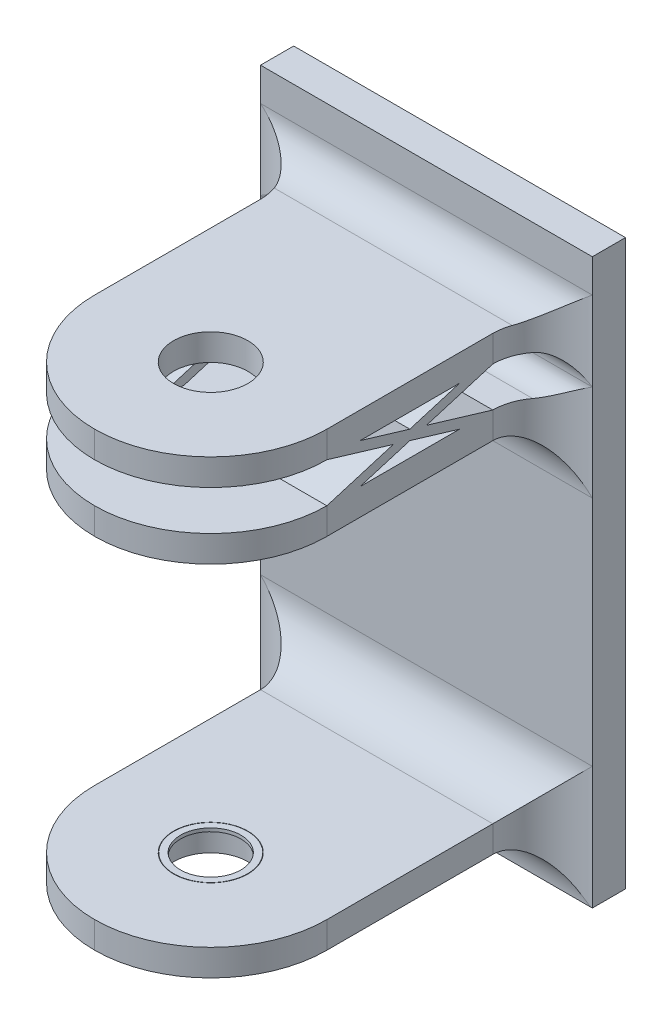
SolidWorks part; units mm, degrees
ref_plane "Plan de face" through (0, 0, 0) normal (1, 0, 0) x (0, 1, 0)
ref_plane "Plan de dessus" through (0, 0, 0) normal (0, 0, 1) x (0, 1, 0)
ref_plane "Plan de droite" through (0, 0, 0) normal (0, 1, 0) x (-1, 0, 0)
sketch "Esquisse1" plane through (0, 0, 0) normal (0, 0, 1) x (0, 1, 0)
  line L1 (0, 0) -> (150, 0)
  line L2 (0, 0) -> (0, 100)
  line L3 (0, 100) -> (150, 100)
  line L4 (150, 0) -> (150, 100)
  dimension "D1" = 150
  dimension "D2" = 100
extrude "Boss.-Extru.1" add sketch "Esquisse1" along normal blind 10
sketch "Esquisse2" plane through (0, 0, 10) normal (0, 0, 1) x (1, 0, 0)
  line L0 (-100, 150) -> (-100, 0) construction
  line L1 (-85, 130) -> (-15, 130)
  line L2 (-85, 130) -> (-85, 122)
  line L3 (-85, 122) -> (-15, 122)
  line L4 (-15, 130) -> (-15, 122)
  line L5 (-85, 150) -> (-15, 150)
  line L6 (0, 0) -> (0, 150) construction
  line L7 (0, 150) -> (-100, 150) construction
  line L8 (-85, 22) -> (-15, 22)
  line L9 (-85, 22) -> (-85, 14)
  line L10 (-85, 14) -> (-15, 14)
  line L11 (-15, 22) -> (-15, 14)
  line L12 (-85, 150) -> (-85, 142)
  line L13 (-85, 142) -> (-15, 142)
  line L14 (-15, 150) -> (-15, 142)
  dimension "D1" = 8
  dimension "D2" = 8
  dimension "D3" = 100
  dimension "D4" = 70
  dimension "D5" = 15
  dimension "D6" = 70
  dimension "D7" = 15
  dimension "D8" = 12
  dimension "D9" = 70
  dimension "D10" = 8
  dimension "D11" = 15
extrude "Boss.-Extru.2" add sketch "Esquisse2" along normal blind 100
fillet "Congé1" radius 35 6 edges at (-85, 126, 110) (-15, 126, 110) (-15, 18, 110) (-85, 18, 110) (-85, 146, 110) (-15, 146, 110)
sketch "Esquisse3" plane through (0, 150, 0) normal (0, 1, 0) x (-1, 0, 0)
  line L0 (0, 10) -> (0, 0) construction
  line L2 (0, 0) -> (100, 0) construction
  circle A0 centre (50, 75) radius 11.2
  dimension "D3" = 22.4
  dimension "D1" = 50
  dimension "D2" = 75
extrude "Enlèv. mat.-Extru.1" cut sketch "Esquisse3" against normal blind 150
fillet "Congé2" radius 15 9 edges at (-15, 18, 10) (-50, 22, 10) (-85, 18, 10) (-50, 14, 10) (-85, 146, 10) (-15, 146, 10) (-15, 126, 10) (-50, 122, 10) (-85, 126, 10)
fillet "Congé3" radius 6 2 edges at (-50, 142, 10) (-50, 130, 10)
sketch "Esquisse4" plane through (0, 0, 0) normal (0, -1, 0) x (1, 0, 0)
  line L0 (-100, 10) -> (0, 10) construction
  line L1 (-85.0784, 7.5) -> (-65.0784, 7.5)
  line L2 (-85.0784, 7.5) -> (-85.0784, 2.5)
  line L3 (-85.0784, 2.5) -> (-65.0784, 2.5)
  line L4 (-65.0784, 7.5) -> (-65.0784, 2.5)
  line L5 (-30.993, 7.5) -> (-10.993, 7.5)
  line L6 (-30.993, 7.5) -> (-30.993, 2.5)
  line L7 (-30.993, 2.5) -> (-10.993, 2.5)
  line L8 (-10.993, 7.5) -> (-10.993, 2.5)
  dimension "D1" = 20
  dimension "D2" = 5
  dimension "D3" = 2.5
  dimension "D4" = 5
  dimension "D5" = 20
  dimension "D6" = 2.5
extrude "Enlèv. mat.-Extru.2" cut sketch "Esquisse4" against normal blind 10
sketch "Esquisse5" plane through (-85, 0, 0) normal (-1, 0, 0) x (0, -1, 0)
  line L0 (-142, 75) -> (-130, 35)
  line L1 (-130, 75) -> (-130, 25) construction
  line L2 (-130, 35) -> (-130, 25)
  line L3 (-130, 25) -> (-142, 65)
  line L4 (-142, 75) -> (-142, 25) construction
  line L5 (-142, 65) -> (-142, 75)
  dimension "D1" = 10
  dimension "D2" = 10
extrude "Boss.-Extru.3" add sketch "Esquisse5" against normal blind 17
sketch "Esquisse7" plane through (-85, 0, 0) normal (-1, 0, 0) x (0, -1, 0)
  line L0 (-142, 25) -> (-142, 35)
  line L1 (-142, 25) -> (-130, 65)
  line L2 (-142, 35) -> (-130, 75)
  line L3 (-130, 65) -> (-130, 75)
  line L4 (-142, 65) -> (-142, 25) construction
  dimension "D1" = 10
extrude "Boss.-Extru.6" add sketch "Esquisse7" against normal blind 17
fillet "Congé4" radius 10 1 edges at (-76.5, 142, 75)
ref_axis "Axe1" through (-50, 150, 0) along (0, 0, 1)
ref_axis "Axe2" through (-50, 14, 110) along (0, 0, -1)
ref_plane "Plan1" through (-50, 0, 0) normal (1, 0, 0) x (0, 0, -1)
mirror "Symétrie1" about plane through (-50, 0, 0) normal (1, 0, 0) of "Boss.-Extru.3", "Boss.-Extru.6"
ref_plane "Plan2" through (-85, 22, 75) normal (0, 0, -1) x (-1, 0, 0)
sketch "Esquisse10" plane through (0, 22, 0) normal (0, 1, 0) x (-1, 0, 0)
  circle A0 centre (50, 75) radius 11.0955
  circle A1 centre (50, 75) radius 9.0955
  dimension "D1" = 2
extrude "Boss.-Extru.7" add sketch "Esquisse10" against normal blind 1 separate body
sketch "Esquisse11" plane through (0, 122, 0) normal (0, -1, 0) x (1, 0, 0)
  circle A0 centre (-50, 75) radius 11.2
  circle A1 centre (-50, 75) radius 9.0955
extrude "Boss.-Extru.8" add sketch "Esquisse11" against normal blind 1
sketch "Esquisse13" plane through (0, 0, 0) normal (1, 0, 0) x (0, 1, 0)
  line L0 (136, 10) -> (150, 10) construction
  line L1 (150, 0) -> (170, 0)
  line L2 (150, 0) -> (150, 10)
  line L3 (150, 10) -> (170, 10)
  line L4 (170, 0) -> (170, 10)
  dimension "D1" = 0
  dimension "D2" = 20
extrude "Boss.-Extru.9" add sketch "Esquisse13" against normal blind 100
fillet "Congé6" radius 10 1 edges at (-50, 150, 10)
